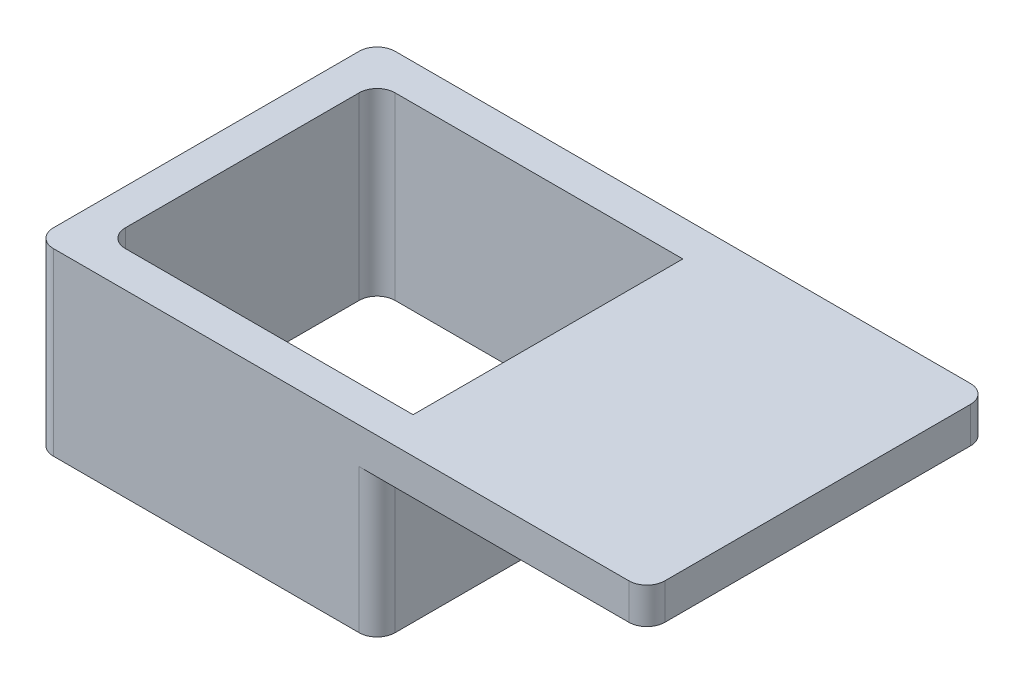
SolidWorks part; units mm, degrees
ref_plane "Alzado" through (0, 0, 0) normal (0, 0, 1) x (1, 0, 0)
ref_plane "Planta" through (0, 0, 0) normal (0, 1, 0) x (1, 0, 0)
ref_plane "Vista lateral" through (0, 0, 0) normal (1, 0, 0) x (0, 0, -1)
sketch "Croquis1" plane through (0, 0, 0) normal (0, 1, 0) x (1, 0, 0)
  line L1 (7.5, 7.5) -> (-7.5, 7.5)
  line L2 (7.5, 7.5) -> (7.5, -7.5)
  line L3 (7.5, -7.5) -> (-7.5, -7.5)
  line L4 (-7.5, 7.5) -> (-7.5, -7.5)
  line L5 (7.5, 7.5) -> (-7.5, -7.5) construction
  line L6 (7.5, -7.5) -> (-7.5, 7.5) construction
  line L7 (9.5, 9.5) -> (-9.5, 9.5)
  line L8 (9.5, 9.5) -> (9.5, -9.5)
  line L9 (9.5, -9.5) -> (-9.5, -9.5)
  line L10 (-9.5, 9.5) -> (-9.5, -9.5)
  line L11 (9.5, 9.5) -> (-9.5, -9.5) construction
  line L12 (9.5, -9.5) -> (-9.5, 9.5) construction
  point P0 (0, 0)
  point P6 (0, 0)
  dimension "D1" = 15
  dimension "D2" = 2
extrude "Saliente-Extruir1" add sketch "Croquis1" along normal blind 10
chamfer "Chaflán1" distance 2 angle 45 1 edges at (7.5, 10, 0)
sketch "Croquis2" plane through (9.5, 0, 0) normal (1, 0, 0) x (0, 0, -1)
  line L0 (9.5, 10) -> (9.5, 0) construction
  line L1 (-9.5, 10) -> (9.5, 10)
  line L2 (-9.5, 10) -> (-9.5, 8)
  line L3 (-9.5, 8) -> (9.5, 8)
  line L4 (9.5, 10) -> (9.5, 8)
  dimension "D1" = 2
extrude "Saliente-Extruir2" add sketch "Croquis2" along normal blind 15
fillet "Redondeo1" radius 1 8 edges at (24.5, 9, -9.5) (24.5, 9, 9.5) (9.5, 4, 9.5) (9.5, 4, -9.5) (-9.5, 5, -9.5) (-9.5, 5, 9.5) (-7.5, 5, 7.5) (-7.5, 5, -7.5)
